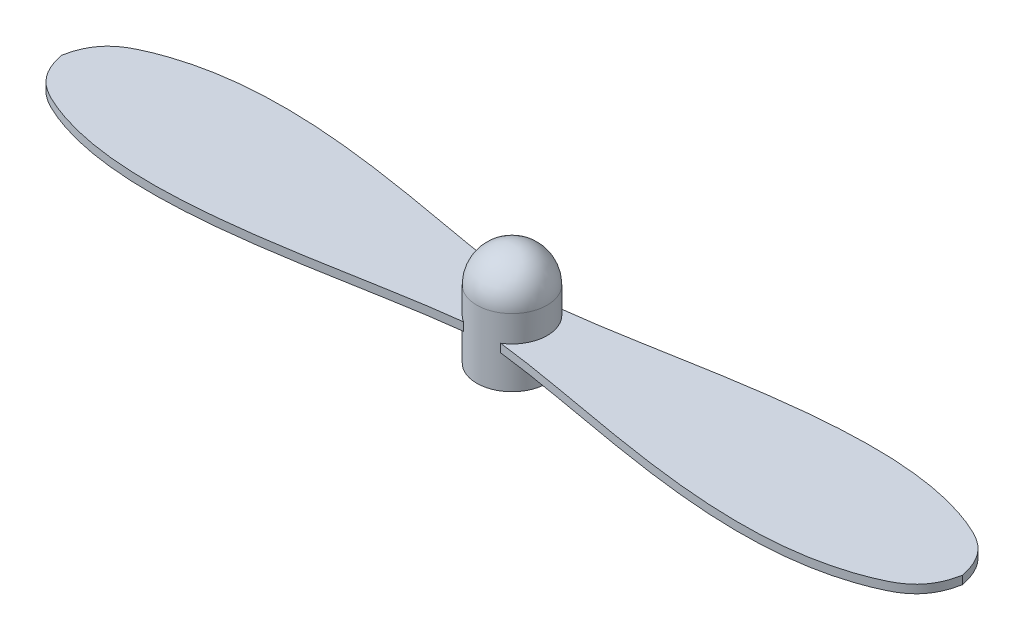
SolidWorks part; units mm, degrees
ref_plane "Front Plane" through (0, 0, 0) normal (0, 0, 1) x (1, 0, 0)
ref_plane "Top Plane" through (0, 0, 0) normal (0, 1, 0) x (1, 0, 0)
ref_plane "Right Plane" through (0, 0, 0) normal (1, 0, 0) x (0, 0, -1)
sketch "Sketch1" plane through (0, 0, 0) normal (0, 1, 0) x (1, 0, 0)
  circle A0 centre (0, 0) radius 2.13
  dimension "D1" = 4.26
extrude "Boss-Extrude1" add sketch "Sketch1" along normal blind 6.22
sketch "Sketch2" plane through (0, 0, 0) normal (0, -1, 0) x (1, 0, 0)
  circle A0 centre (0, 0) radius 0.5
  dimension "D1" = 1
extrude "Cut-Extrude1" cut sketch "Sketch2" against normal blind 5
fillet "Fillet1" radius 2.13 1 edges at (0, 6.22, 2.13)
ref_plane "Plane1" through (0, 2, 0) normal (0, -1, 0) x (-1, 0, 0)
sketch "Sketch3" plane through (0, 2, 0) normal (0, -1, 0) x (-1, 0, 0)
  line L0 (27.225, 0) -> (-27.225, 0) construction
  line L1 (0, 27.225) -> (0, -27.225) construction
  circle A0 centre (0, 0) radius 27.225
  circle A1 centre (0, 0) radius 2.13 construction
  circle A2 centre (0, 0) radius 2.13
  spline S0 degree 3 poles (27.225, 0) (26.8837, 1.7076) (19.5902, 6.2181) (7.7911, 2.5647) (1.1217, 1.8107) knots 0 0 0 0 0.130362 1 1 1 1
  spline S1 degree 3 poles (27.225, 0) (26.8837, -1.7076) (19.5902, -6.2181) (7.7911, -2.5647) (1.1217, -1.8107) knots 0 0 0 0 0.130362 1 1 1 1
  spline S2 degree 3 poles (-27.225, 0) (-26.8837, 1.7076) (-19.5902, 6.2181) (-7.7911, 2.5647) (-1.1217, 1.8107) knots 0 0 0 0 0.130362 1 1 1 1
  spline S3 degree 3 poles (-27.225, 0) (-26.8837, -1.7076) (-19.5902, -6.2181) (-7.7911, -2.5647) (-1.1217, -1.8107) knots 0 0 0 0 0.130362 1 1 1 1
  dimension "D1" = 54.45
extrude "Boss-Extrude2" add sketch "Sketch3" against normal blind 0.5 contours S1 S0 A2 | S2 S3 A2 region at (-14.9398, 2, 0) region at (14.9385, 2, 0)
